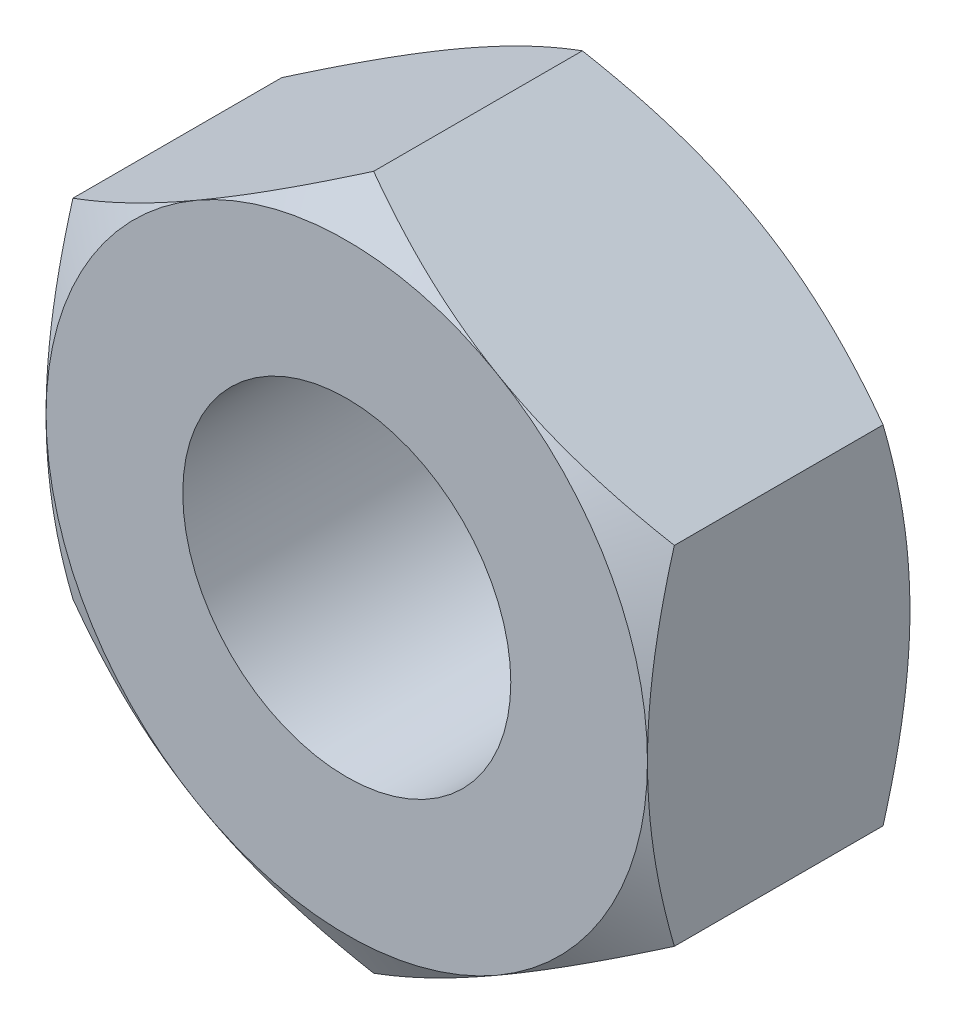
SolidWorks part; units mm, degrees
ref_plane "Front" through (0, 0, 0) normal (0, 0, 1) x (1, 0, 0)
ref_plane "Top" through (0, 0, 0) normal (0, 1, 0) x (1, 0, 0)
ref_plane "Right" through (0, 0, 0) normal (1, 0, 0) x (0, 0, -1)
sketch "Sketch1" plane through (0, 0, 0) normal (0, 0, 1) x (1, 0, 0)
  line L1 (-2.75, 1.5877) -> (-2.75, -1.5877)
  line L2 (-2.75, -1.5877) -> (0, -3.1754)
  line L3 (0, -3.1754) -> (2.75, -1.5877)
  line L4 (2.75, -1.5877) -> (2.75, 1.5877)
  line L5 (2.75, 1.5877) -> (0, 3.1754)
  line L6 (0, 3.1754) -> (-2.75, 1.5877)
  circle A0 centre (0, 0) radius 2.75 construction
  circle A1 centre (0, 0) radius 1.5 construction
  point P10 (0, 1.5)
  dimension "hex" = 5.5
  dimension "dia" = 3
extrude "Extrude1" add sketch "Sketch1" along normal mid plane 2.4
sketch "Sketch4" plane through (0, 0, -1.2) normal (0, 0, -1) x (-1, 0, 0)
  circle A0 centre (0, 0) radius 1.5 construction
  circle A1 centre (0, 0) radius 1.5
sketch "Sketch10" plane through (0, 0, 1.2) normal (0, 0, 1) x (1, 0, 0)
  circle A0 centre (0, 0) radius 1.5 construction
  circle A1 centre (0, 0) radius 1.5
extrude "Cut-Extrude2" cut sketch "Sketch10" against normal through all draft 45
sketch "Sketch11" plane through (0, 0, -1.2) normal (0, 0, -1) x (-1, 0, 0)
  circle A0 centre (0, 0) radius 1.5 construction
  circle A1 centre (0, 0) radius 1.5
extrude "Cut-Extrude3" cut sketch "Sketch11" against normal through all draft 45
sketch "Sketch13" plane through (0, 0, -1.2) normal (0, 0, -1) x (-1, 0, 0)
  circle A0 centre (0, 0) radius 1.5 construction
  circle A1 centre (0, 0) radius 1.5
extrude "Boss-Extrude1" add sketch "Sketch13" against normal up to vertex (2.4 mm away) separate body up to point (-2.75, 1.5877, 1.2)
curve "Helix/Spiral3" [suppressed] pitch 0.5 height 2.4 turns 4.8
sketch "Sketch12" plane through (0, 0, 0) normal (1, 0, 0) x (0, 0, -1)
  line L0 (1.6375, 1.5) -> (1.2, 1.5)
  line L1 (1.6375, 1.5) -> (1.45, 1.1752)
  line L2 (1.45, 1.1752) -> (1.3875, 1.1752)
  line L3 (1.3875, 1.1752) -> (1.2, 1.5)
  line L4 (1.4187, 1.1752) -> (1.4187, 1.5) construction
  line L5 (1.2937, 1.3376) -> (1.5437, 1.3376) construction
  dimension "D1" = 60
  dimension "D2" = 0.0625
  dimension "D3" = 0.25
sweep "Cut-Sweep1" [suppressed] cut profiles "Sketch12" path "Helix/Spiral3"
combine bodies "Combine1" operation type subtract main body 116 bodies to subtract 117
sketch "Sketch7" plane through (0, 0, 1.2) normal (0, 0, 1) x (1, 0, 0)
  circle A0 centre (0, 0) radius 2.75 construction
  circle A1 centre (0, 0) radius 2.75
extrude "Extrude2" cut sketch "Sketch7" against normal blind 25.4 draft 60 flip side to cut
mirror "Mirror2" about plane through (0, 0, 0) normal (0, 0, 1) of "Extrude2"
sketch "Sketch8" plane through (0, 0, 1.2) normal (0, 0, 1) x (1, 0, 0)
  line L0 (-1.0607, 1.0607) -> (0, 0) construction
  line L1 (0, -1.5313) -> (0, 1.5313) construction
  circle A1 centre (0, 0) radius 1.5 construction
  point P0 (-1.0607, 1.0607)
  dimension "D1" = 45
sketch "Sketch14" plane through (0, 0, 1.2) normal (0, 0, 1) x (1, 0, 0)
  line L0 (0, 0) -> (-1.5, 0) construction
  circle A0 centre (0, 0) radius 1.5 construction
equation "\"D3@Helix/Spiral3\" = \"length@Extrude1\" "
equation "\"D2@Sketch12\" = \"D4@Helix/Spiral3\"*.125"
equation "\"D3@Sketch12\" = \"D4@Helix/Spiral3\"*.50"
